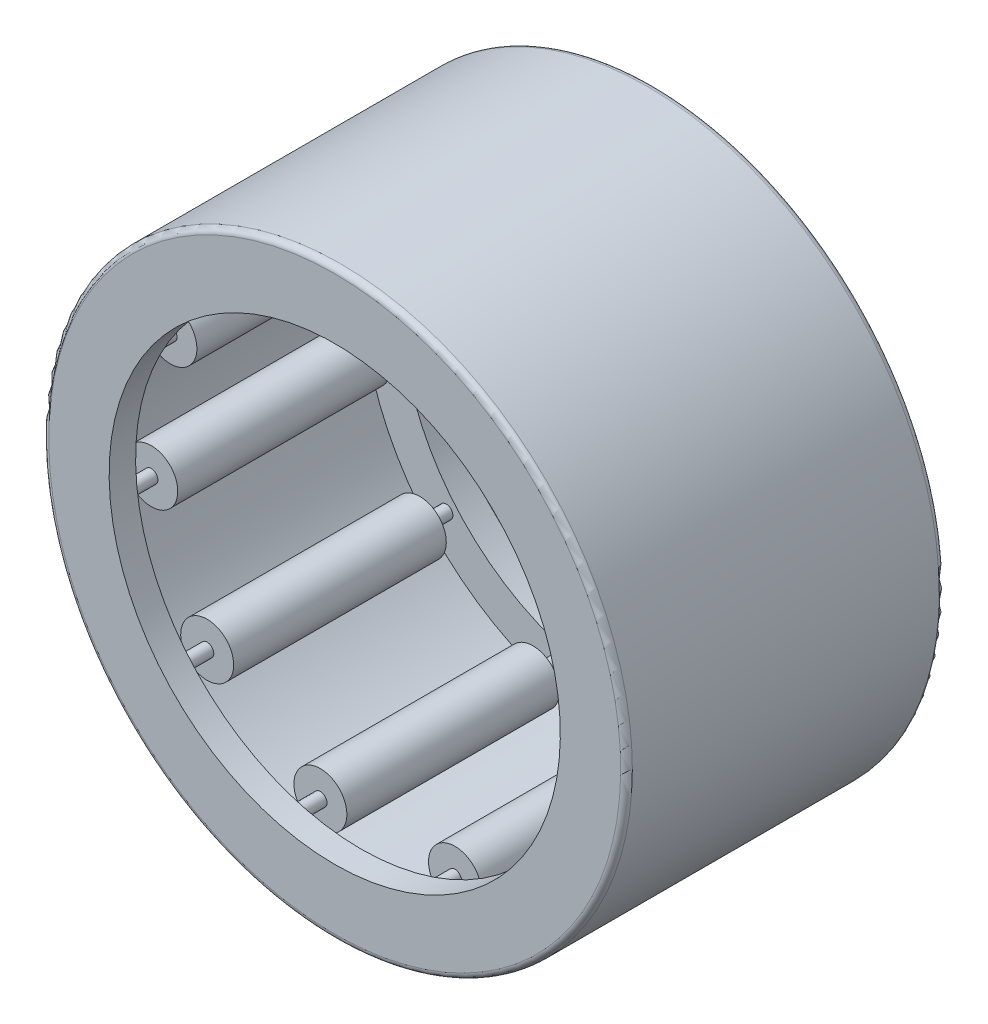
SolidWorks part; units mm, degrees
ref_plane "Front Plane" through (0, 0, 0) normal (0, 0, 1) x (1, 0, 0)
ref_plane "Top Plane" through (0, 0, 0) normal (0, 1, 0) x (1, 0, 0)
ref_plane "Right Plane" through (0, 0, 0) normal (1, 0, 0) x (0, 0, -1)
sketch "Sketch1" plane through (0, 0, 0) normal (1, 0, 0) x (0, 0, -1)
  line L0 (-4.7625, 0) -> (4.7625, 0) construction
  line L1 (0, 0) -> (0, 8.7249) construction
  line L2 (-4.7625, 0) -> (-4.7625, 8.7249) construction
  line L3 (-4.7625, 8.7249) -> (4.7625, 8.7249)
  line L4 (4.7625, 8.7249) -> (4.7625, 0) construction
  line L5 (4.7625, 0) -> (3.9709, 0) construction
  line L6 (3.9709, 0) -> (3.9709, 7.9333) construction
  line L7 (3.9709, 7.9333) -> (-3.9709, 7.9333)
  line L8 (-3.9709, 7.9333) -> (-3.9709, 0) construction
  line L9 (-3.9709, 0) -> (-4.7625, 0) construction
  line L10 (-4.7625, 8.7249) -> (-4.7625, 6.7458)
  line L11 (-4.7625, 6.7458) -> (-3.9709, 6.7458)
  line L12 (-3.9709, 6.7458) -> (-3.9709, 7.9333)
  line L13 (3.9709, 8.7249) -> (3.9709, 7.9333) construction
  line L14 (3.9709, 7.9333) -> (3.9709, 6.7458)
  line L15 (3.9709, 6.7458) -> (4.7625, 6.7458)
  line L16 (4.7625, 6.7458) -> (4.7625, 8.7249)
  line L17 (3.9709, 7.9333) -> (3.9709, 7.1416) construction
  line L18 (3.9709, 7.1416) -> (3.9709, 6.35) construction
  point P5 (0, 6.35)
  dimension "Width" = 9.525
  dimension "OD" = 17.4498
  dimension "Shaft Dia" = 12.7
revolve "Revolve1" add sketch "Sketch1" angle 360 about L0
sketch "Sketch2" plane through (0, 0, 0) normal (1, 0, 0) x (0, 0, -1)
  line L0 (3.9709, 7.9333) -> (-3.9709, 7.9333) construction
  line L1 (-3.1792, 7.1416) -> (3.1792, 7.1416) construction
  line L2 (-3.1792, 7.1416) -> (-3.1792, 7.9333) construction
  line L3 (-3.1792, 7.9333) -> (3.1792, 7.9333)
  line L4 (3.1792, 7.1416) -> (3.1792, 7.9333) construction
  line L5 (3.9709, 6.7458) -> (4.7625, 6.7458) construction
  line L6 (-3.9709, 7.1416) -> (-3.1792, 7.1416) construction
  line L7 (3.1792, 7.1416) -> (3.9709, 7.1416) construction
  line L8 (-4.7625, 6.7458) -> (-3.9709, 6.7458) construction
  line L9 (-3.1792, 7.3395) -> (-3.1792, 6.9437) construction
  line L10 (-3.9709, 7.1416) -> (-3.9709, 6.7458) construction
  line L11 (-3.1792, 7.9333) -> (-3.1792, 7.3395)
  line L12 (3.1792, 7.9333) -> (3.1792, 7.3395)
  line L13 (3.1792, 7.3395) -> (-3.1792, 7.3395)
  line L14 (0, 7.9333) -> (0, 6.35) construction
  line L15 (-3.9709, 6.7458) -> (-3.9709, 7.9333) construction
  line L16 (-3.1792, 6.9437) -> (-3.9709, 6.9437) construction
  line L17 (0, 0) -> (4.7625, 0) construction
  line L31 (4.7625, -8.7249) -> (4.7625, 8.7249) construction
  point P16 (0, 7.1416)
revolve "Revolve2" add sketch "Sketch2" angle 360 about L1
sketch "Sketch3" plane through (0, 0, 0) normal (1, 0, 0) x (0, 0, -1)
  line L0 (3.9709, 7.9333) -> (3.9709, 6.7458) construction
  line L1 (-3.9709, 7.1416) -> (3.9709, 7.1416)
  line L2 (-3.9709, 7.1416) -> (-3.9709, 7.3395)
  line L3 (-3.9709, 7.3395) -> (3.9709, 7.3395)
  line L4 (3.9709, 7.1416) -> (3.9709, 7.3395)
  line L5 (0, 0) -> (4.7625, 0) construction
  line L6 (4.7625, -8.7249) -> (4.7625, 8.7249) construction
revolve "Revolve3" add sketch "Sketch3" angle 360 about L1
ref_axis "Axis1" through (0, 0, -4.7625) along (0, 0, 1)
pattern_circular "CirPattern1" count 11 every 32.727 about axis through (0, 0, -4.7625) along (0, 0, 1) of bodies 166 167
fillet "Fillet1" radius 0.1745 2 edges at (0, -8.7249, -4.7625) (0, -8.7249, 4.7625)
sketch "Sketch4" plane through (0, 0, 0) normal (1, 0, 0) x (0, 0, -1)
  line L1 (4.588, 6.35) -> (3.1792, 6.35)
  line L2 (4.588, 6.35) -> (4.588, 6.7458)
  line L3 (4.588, 6.7458) -> (3.1792, 6.7458)
  line L4 (3.1792, 6.35) -> (3.1792, 6.7458)
  line L5 (-4.7625, 6.7458) -> (-3.9709, 6.7458) construction
  line L6 (4.588, -8.7249) -> (4.588, 8.7249) construction
  line L7 (3.1792, 7.9333) -> (3.1792, 7.3395) construction
revolve "Revolve4" [suppressed] add sketch "Sketch4" angle 360 about L0
sketch "Sketch5" plane through (0, 0, 0) normal (1, 0, 0) x (0, 0, -1)
  line L0 (-4.588, 8.7249) -> (-4.588, -8.7249) construction
  line L1 (-3.1792, 6.35) -> (-4.588, 6.35)
  line L2 (-3.1792, 6.35) -> (-3.1792, 6.7458)
  line L3 (-3.1792, 6.7458) -> (-4.588, 6.7458)
  line L4 (-4.588, 6.35) -> (-4.588, 6.7458)
  line L6 (-3.1792, 7.9333) -> (-3.1792, 7.3395) construction
  line L7 (-4.7625, 6.7458) -> (-3.9709, 6.7458) construction
revolve "Revolve5" [suppressed] add sketch "Sketch5" angle 360 about L0
sketch "Front View" plane through (0, 0, 0) normal (0, 0, 1) x (1, 0, 0)
  circle A0 centre (0, 0) radius 6.35 construction
  circle A1 centre (0, 0) radius 8.7249 construction
  dimension "OD" = 17.4498
  dimension "ID" = 12.7
sketch "Right View" plane through (0, 0, 0) normal (1, 0, 0) x (0, 0, -1)
  line L0 (-4.7625, 8.7249) -> (4.7625, 8.7249) construction
  dimension "Width" = 9.525
ref_axis "Center Axis 1" through (0, 0, -4.588) along (0, 0, 1)
ref_plane "Contact Plane 1" through (0, 0, 4.7625) normal (0, 0, 1) x (1, 0, 0)
ref_plane "Contact Plane 2" through (0, 0, -4.7625) normal (0, 0, -1) x (-1, 0, 0)
equation "\"Rollers@CirPattern1\" = \"OD@Sketch1\"*16"
equation "\"D1@Fillet1\" = \"OD@Sketch1\"*.01"
equation "\"Angle@CirPattern1\"= 360 / \"Rollers@CirPattern1\""
equation "\"OD@Front View\"=\"OD@Sketch1\""
equation "\"ID@Front View\"=\"Shaft Dia@Sketch1\""
equation "\"Width@Right View\"=\"Width@Sketch1\""
